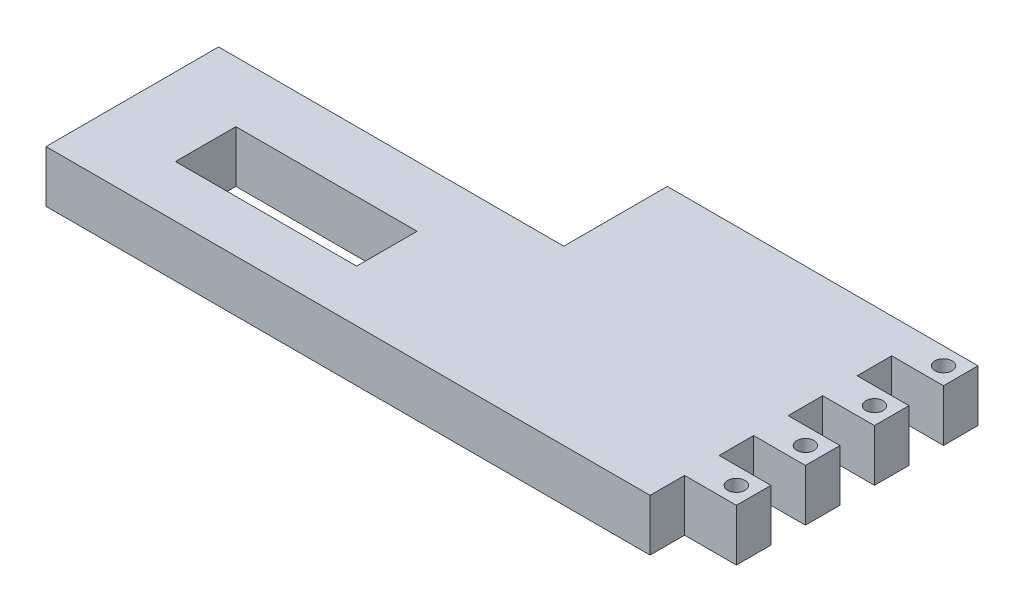
SolidWorks part; units mm, degrees
ref_plane "Front Plane" through (0, 0, 0) normal (0, 0, 1) x (1, 0, 0)
ref_plane "Top Plane" through (0, 0, 0) normal (0, 1, 0) x (1, 0, 0)
ref_plane "Right Plane" through (0, 0, 0) normal (1, 0, 0) x (0, 0, -1)
sketch "Sketch1" plane through (0, 0, 0) normal (0, 1, 0) x (1, 0, 0)
  line L0 (-40, 0) -> (0, 0)
  line L1 (0, 0) -> (0, 12)
  line L2 (0, 12) -> (36, 12)
  line L3 (36, 0) -> (36, 4)
  line L4 (36, 4) -> (30, 4)
  line L5 (30, 4) -> (30, 8)
  line L6 (30, 8) -> (36, 8)
  line L7 (36, 8) -> (36, 12)
  line L8 (30, -4) -> (36, -4)
  line L9 (36, -4) -> (36, -8)
  line L10 (36, -8) -> (30, -8)
  line L11 (30, -12) -> (30, -8)
  line L12 (36, 0) -> (30, 0)
  line L13 (30, 0) -> (30, -4)
  line L14 (30, -20) -> (-40, -20)
  line L15 (-40, -20) -> (-40, 0)
  line L16 (30, -12) -> (36, -12)
  line L17 (36, -12) -> (36, -16)
  line L18 (36, -16) -> (30, -16)
  line L19 (30, -16) -> (30, -20)
  dimension "D1" = 4
  dimension "D2" = 30
  dimension "D3" = 12
  dimension "D4" = 6
  dimension "D5" = 4
  dimension "D6" = 4
  dimension "D7" = 20
  dimension "D8" = 40
  dimension "D9" = 4
  dimension "D10" = 4
  dimension "D11" = 4
  dimension "D12" = 4
extrude "Boss-Extrude1" add sketch "Sketch1" along normal blind 6
sketch "Sketch2" plane through (0, 6, 0) normal (0, 1, 0) x (1, 0, 0)
  line L0 (0, 12) -> (0, 0) construction
  line L1 (-31, -7) -> (-10, -7)
  line L2 (-31, -7) -> (-31, -14)
  line L3 (-31, -14) -> (-10, -14)
  line L4 (-10, -7) -> (-10, -14)
  line L5 (-40, -20) -> (30, -20) construction
  dimension "D1" = 7
  dimension "D2" = 21
  dimension "D3" = 10
  dimension "D4" = 6
extrude "Cut-Extrude1" cut sketch "Sketch2" against normal through all
sketch "Sketch3" plane through (0, 6, 0) normal (0, 1, 0) x (1, 0, 0)
  line L0 (36, 8) -> (36, 12) construction
  line L1 (36, 0) -> (36, 4) construction
  line L2 (36, -8) -> (36, -4) construction
  line L3 (36, -16) -> (36, -12) construction
  circle A0 centre (34, 10) radius 1
  circle A1 centre (34, 2) radius 1
  circle A2 centre (34, -6) radius 1
  circle A3 centre (34, -14) radius 1
  point P4 (36, 10)
  point P13 (36, 2)
  point P16 (36, -6)
  point P19 (36, -14)
  dimension "D1" = 2
  dimension "D2" = 2
extrude "Cut-Extrude2" cut sketch "Sketch3" against normal through all
